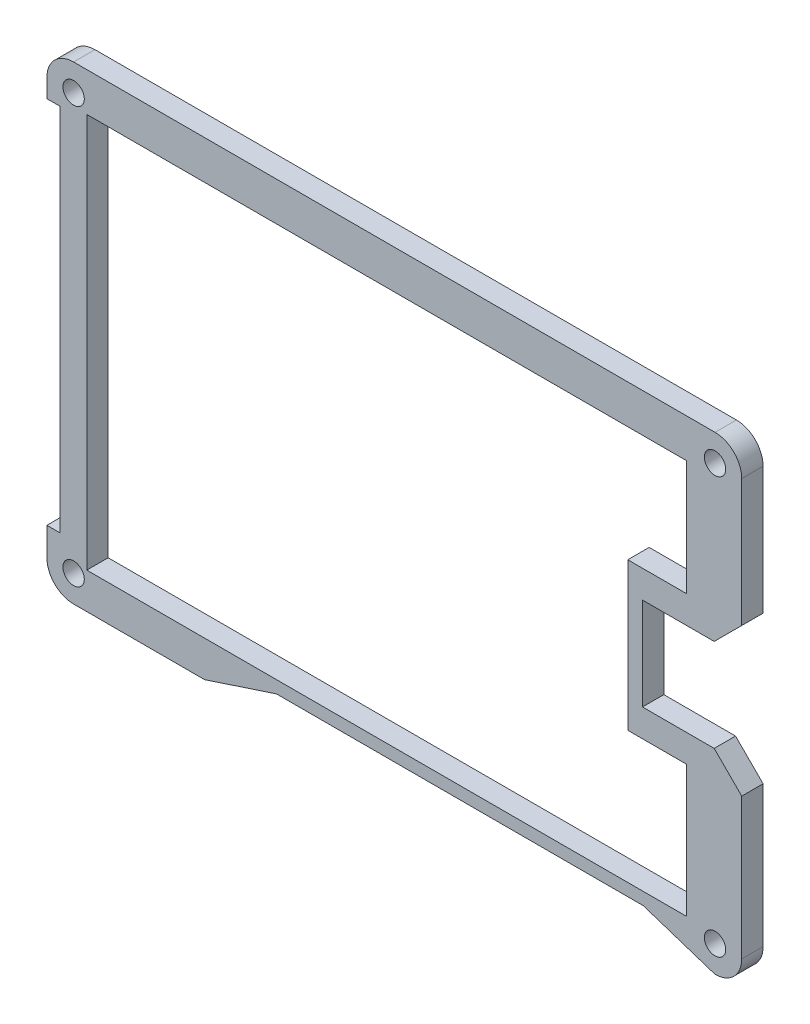
SolidWorks part; units mm, degrees
ref_plane "Front Plane" through (0, 0, 0) normal (0, 0, 1) x (1, 0, 0)
ref_plane "Top Plane" through (0, 0, 0) normal (0, 1, 0) x (1, 0, 0)
ref_plane "Right Plane" through (0, 0, 0) normal (1, 0, 0) x (0, 0, -1)
sketch "Sketch1" plane through (0, 0, 0) normal (0, 0, 1) x (1, 0, 0)
  line L0 (-309.8086, 128.8851) -> (-305.8779, 128.8851) construction
  line L1 (-305.8779, 128.8851) -> (-301.9473, 132.8157) construction
  line L2 (-301.9473, 132.8157) -> (-301.9473, 150.9704) construction
  line L3 (-305.7573, 154.7804) -> (-397.2471, 154.7804) construction
  line L4 (-401.0571, 150.9566) -> (-401.0571, 148.341) construction
  line L5 (-401.0571, 148.341) -> (-399.1521, 148.341) construction
  line L6 (-399.1521, 148.341) -> (-399.1521, 95.6449) construction
  line L7 (-399.1521, 95.6449) -> (-401.0571, 95.6449) construction
  line L8 (-401.0571, 95.6449) -> (-401.0571, 91.6593) construction
  line L9 (-378.5565, 87.8217) -> (-397.2472, 87.8217) construction
  line L10 (-368.3165, 91.1883) -> (-378.5565, 87.8217) construction
  line L11 (-315.9973, 91.1883) -> (-368.3165, 91.1883) construction
  line L12 (-315.9973, 91.1883) -> (-305.7573, 87.8217) construction
  line L13 (-301.9473, 91.6317) -> (-301.9473, 111.7465) construction
  line L14 (-305.8779, 115.6771) -> (-301.9473, 111.7465) construction
  line L15 (-309.8086, 115.6771) -> (-305.8779, 115.6771) construction
  line L16 (-309.8086, 128.8851) -> (-305.8779, 128.8851)
  line L17 (-305.8779, 128.8851) -> (-301.9473, 132.8157)
  line L18 (-301.9473, 132.8157) -> (-301.9473, 150.9704)
  line L19 (-305.7573, 154.7804) -> (-397.2471, 154.7804)
  line L20 (-401.0571, 150.9566) -> (-401.0571, 148.341)
  line L21 (-401.0571, 148.341) -> (-399.1521, 148.341)
  line L22 (-399.1521, 148.341) -> (-399.1521, 95.6449)
  line L23 (-399.1521, 95.6449) -> (-401.0571, 95.6449)
  line L24 (-401.0571, 95.6449) -> (-401.0571, 91.6593)
  line L25 (-378.5565, 87.8217) -> (-397.2472, 87.8217)
  line L26 (-368.3165, 91.1883) -> (-378.5565, 87.8217)
  line L27 (-315.9973, 91.1883) -> (-368.3165, 91.1883)
  line L28 (-315.9973, 91.1883) -> (-305.7573, 87.8217)
  line L29 (-301.9473, 91.6317) -> (-301.9473, 111.7465)
  line L30 (-305.8779, 115.6771) -> (-301.9473, 111.7465)
  line L31 (-309.8086, 115.6771) -> (-305.8779, 115.6771)
  line L32 (-309.8086, 128.8851) -> (-316.1078, 128.8851)
  line L33 (-316.1078, 128.8851) -> (-316.1078, 115.6771)
  line L34 (-316.1078, 115.6771) -> (-309.8086, 115.6771)
  line L35 (-395.3675, 92.9525) -> (-395.3675, 149.2432) construction
  line L36 (-395.3675, 92.9525) -> (-395.3675, 149.2432)
  line L37 (-395.3675, 149.2432) -> (-309.8086, 149.2432) construction
  line L38 (-395.3675, 149.2432) -> (-309.8086, 149.2432)
  line L39 (-395.3675, 92.9525) -> (-309.8086, 92.9525) construction
  line L40 (-395.3675, 92.9525) -> (-309.8086, 92.9525)
  line L41 (-309.8086, 111.7465) -> (-318.2033, 111.7465)
  line L42 (-309.8086, 115.6771) -> (-309.8086, 92.9525) construction
  line L43 (-318.2033, 111.7465) -> (-318.2033, 132.8157)
  line L44 (-318.2033, 134.8668) -> (-318.2033, 116.6297) construction
  line L45 (-318.2033, 132.8157) -> (-309.8086, 132.8157)
  line L46 (-309.8086, 149.2432) -> (-309.8086, 128.8851) construction
  line L47 (-309.8086, 132.8157) -> (-309.8086, 149.2432)
  line L48 (-309.8086, 111.7465) -> (-309.8086, 92.9525)
  arc A0 (-301.9473, 150.9704) -> (-305.7573, 154.7804) centre (-305.7573, 150.9704) ccw construction
  arc A1 (-397.2471, 154.7804) -> (-401.0571, 150.9566) centre (-397.2471, 150.9704) ccw construction
  arc A2 (-401.0571, 91.6593) -> (-397.2472, 87.8217) centre (-397.2472, 91.6317) ccw construction
  arc A3 (-305.7573, 87.8217) -> (-301.9473, 91.6317) centre (-305.7573, 91.6317) ccw construction
  arc A4 (-301.9473, 150.9704) -> (-305.7573, 154.7804) centre (-305.7573, 150.9704) ccw
  arc A5 (-397.2471, 154.7804) -> (-401.0571, 150.9566) centre (-397.2471, 150.9704) ccw
  arc A6 (-401.0571, 91.6593) -> (-397.2472, 87.8217) centre (-397.2472, 91.6317) ccw
  arc A7 (-305.7573, 87.8217) -> (-301.9473, 91.6317) centre (-305.7573, 91.6317) ccw
  dimension "D1" = 6.2992
extrude "Boss-Extrude1" add sketch "Sketch1" along normal blind 3.048
sketch "Sketch2" plane through (0, 0, 0) normal (0, 0, -1) x (-1, 0, 0)
  circle A0 centre (305.7573, 150.9704) radius 1.3559
  circle A1 centre (397.2471, 150.9704) radius 1.3559
  circle A2 centre (397.2472, 91.6317) radius 1.3559
  circle A3 centre (305.7573, 91.6317) radius 1.3559
  dimension "D1" = 2.7118
extrude "Cut-Extrude1" cut sketch "Sketch2" against normal through all
sketch "Sketch3" plane through (0, 0, 0) normal (0, 0, -1) x (-1, 0, 0)
  circle A0 centre (305.7573, 150.9704) radius 1.524
  circle A1 centre (397.2471, 150.9704) radius 1.524
  circle A2 centre (397.2472, 91.6317) radius 1.524
  circle A3 centre (305.7573, 91.6317) radius 1.524
  dimension "D1" = 3.048
extrude "Cut-Extrude2" cut sketch "Sketch3" against normal through all
